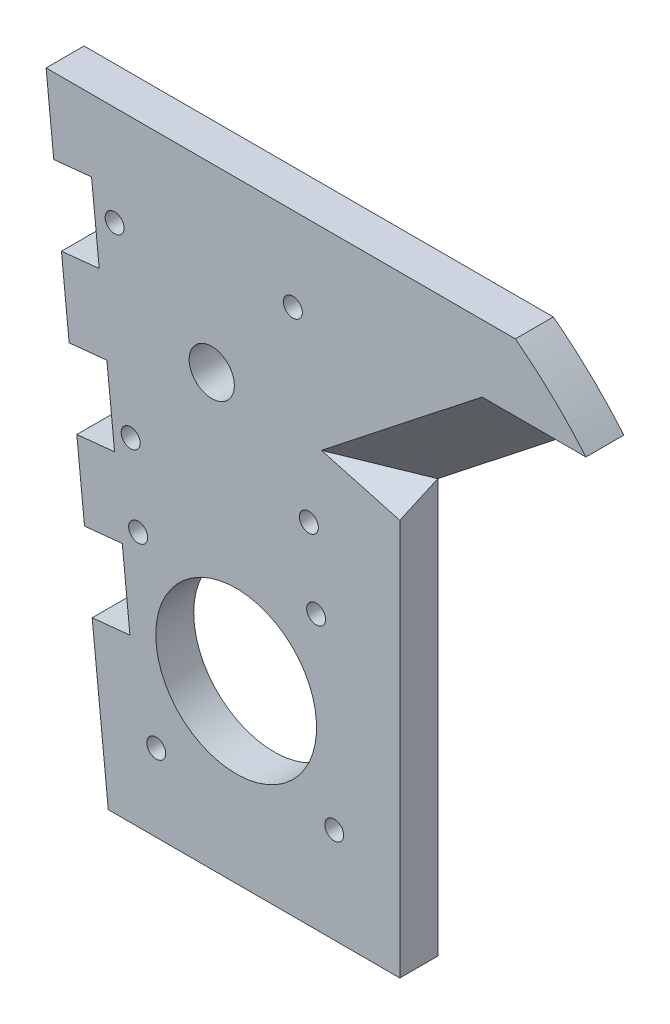
SolidWorks part; units mm, degrees
ref_plane "Front Plane" through (0, 0, 0) normal (0, 0, 1) x (1, 0, 0)
ref_plane "Top Plane" through (0, 0, 0) normal (0, 1, 0) x (1, 0, 0)
ref_plane "Right Plane" through (0, 0, 0) normal (1, 0, 0) x (0, 0, -1)
sketch "Sketch1" plane through (0, 0, 0) normal (0, 0, 1) x (1, 0, 0)
  line L0 (-43.6414, 47.6599) -> (-41.6177, 27.7626)
  line L1 (-43.6414, 47.6599) -> (80, 47.6599)
  line L2 (-37.5704, -12.0321) -> (-27.6217, -11.0203)
  line L3 (-27.2617, -113.389) -> (95, -113.389)
  line L4 (95, 30) -> (95, -113.389)
  line L5 (71.2187, 30) -> (98.5875, 30) construction
  line L6 (-18.1149, -203.3229) -> (-5.8407, -324.0059) construction
  line L7 (-41.6177, 27.7626) -> (-31.6691, 28.7744)
  line L8 (-31.6691, 28.7744) -> (-29.6454, 8.8771)
  line L9 (-29.6454, 8.8771) -> (-39.594, 7.8652)
  line L10 (-39.594, 7.8652) -> (-37.5704, -12.0321)
  line L11 (-27.6217, -11.0203) -> (-25.598, -30.9176)
  line L12 (-25.598, -30.9176) -> (-35.5467, -31.9295)
  line L13 (-35.5467, -31.9295) -> (-33.523, -51.8268)
  line L14 (-33.523, -51.8268) -> (-23.5743, -50.815)
  line L15 (-23.5743, -50.815) -> (-21.5506, -70.7123)
  line L16 (-21.5506, -70.7123) -> (-31.4993, -71.7242)
  line L17 (-31.4993, -71.7242) -> (-27.2617, -113.389)
  line L18 (71.2187, 30) -> (98.5875, 30) construction
  line L19 (95, 30) -> (98.5875, 30)
  circle A0 centre (0, 0) radius 5.9585
  spline S0 degree 2 poles (80, 47.6599) (90.2611, 39.8512) (98.5875, 30) knots 0 0 0 1 1 1
  dimension "D1" = 95
extrude "Boss-Extrude1" add sketch "Sketch1" along normal blind 10
ref_axis "Axis1" through (-681.2985, -580.132, 0) along (0.7856, 0.6188, 0)
sketch "Sketch3" plane through (0, 0, 0) normal (0, 0, -1) x (-1, 0, 0)
  line L0 (-95, 30) -> (-65, 30)
  line L1 (-95, -113.389) -> (-95, 30) construction
  line L2 (-65, 30) -> (-28, 0.8563)
  line L3 (-28, -15) -> (-95, -15)
  line L4 (-95, -15) -> (-95, 30)
  line L5 (681.2985, -580.132) -> (-401.1924, 272.512) construction
  line L6 (-28, 0.8563) -> (-28, -15)
  dimension "D1" = 30
  dimension "D2" = 30
  dimension "D3" = 45
  dimension "D4" = 67
sketch "Sketch4" plane through (0, 0, 0) normal (0, 0, -1) x (-1, 0, 0)
  line L0 (0, 0) -> (-6.4368, -67.1924) construction
  line L1 (-3.2184, -33.5962) -> (-50.6414, -29.0532) construction
  circle A0 centre (-6.4368, -67.1924) radius 21.1868
  circle A1 centre (25.5857, 21.365) radius 2.5
  circle A2 centre (-21.365, 25.5857) radius 2.5
  circle A3 centre (-6.4368, -67.1924) radius 3.175 construction
  circle A4 centre (14.6273, -93.0263) radius 2.5 construction
  circle A5 centre (-32.2708, -88.2565) radius 2.5 construction
  circle A6 centre (19.3971, -46.1283) radius 2.5 construction
  circle A7 centre (-27.501, -41.3584) radius 2.5 construction
  circle A8 centre (14.6273, -93.0263) radius 2.5
  circle A9 centre (-32.2708, -88.2565) radius 2.5
  circle A10 centre (19.3971, -46.1283) radius 2.5
  circle A11 centre (-27.501, -41.3584) radius 2.5
  circle A12 centre (-25.5857, -21.365) radius 2.5
  circle A13 centre (21.365, -25.5857) radius 2.5
extrude "Cut-Extrude4" cut sketch "Sketch4" against normal blind 10
sketch "Sketch5" plane through (-775.1664, -380.1547, 157.4414) normal (0.3654, -0.4639, 0.807) x (0.899, -0.0492, -0.4353)
  line L0 (830.5963, 510.2094) -> (803.6276, 502.9612) construction
  line L1 (845.9324, 510.7378) -> (653.1914, 500.0195)
  line L2 (845.9324, 510.7378) -> (845.9324, 468.7472)
  line L3 (845.9324, 468.7472) -> (653.1914, 468.7472)
  line L4 (653.1914, 500.0195) -> (653.1914, 468.7472)
  line L5 (830.5963, 510.2094) -> (803.6276, 502.9612) construction
  line L8 (804.8653, 508.454) -> (834.1696, 510.0836)
  line L9 (829.4687, 515.0665) -> (804.8653, 508.454)
  line L10 (804.8653, 508.454) -> (834.1696, 510.0836) construction
  spline S1 degree 2 poles (684.7348, -478.6879) (1410.3426, 1033.8467) (-168.4762, 451.0398) knots 0.486074 0.486074 0.486074 0.513978 0.513978 0.513978 only from (834.1696, 510.0836) to (829.4687, 515.0665)
  point P9 (829.0739, 509.8003)
  dimension "D1" = 0
extrude "Cut-Extrude5" cut sketch "Sketch5" along normal blind 24
sketch "Sketch6" plane through (0, 30, 0) normal (0, -1, 0) x (1, 0, 0)
  line L0 (95, 10) -> (71.2187, 10)
  line L1 (71.2187, 10) -> (98.5875, 10) construction
  line L2 (71.2187, 10) -> (93.3065, 0)
  line L3 (95, 0) -> (65, 0) construction
  line L4 (95, 0) -> (98.5875, 0)
  line L5 (98.5875, 0) -> (98.5875, 10)
  line L6 (98.5875, 10) -> (95, 10)
  line L7 (95, 10) -> (95, 0)
  line L8 (95, 0) -> (98.5875, 0)
  line L9 (98.5875, 0) -> (98.5875, 10)
  line L10 (98.5875, 10) -> (95, 10)
  line L12 (93.3065, 0) -> (95, 0)
  line L13 (93.3065, 0) -> (95, 0)
  line M5 (95, 0) -> (98.5875, 0)
  line M6 (98.5875, 0) -> (98.5875, 10)
  line M7 (98.5875, 10) -> (95, 10)
  line M8 (95, 10) -> (95, 0)
  dimension "D1" = 0
extrude "Cut-Extrude8" cut sketch "Sketch6" along normal blind 24 contours M8 M5 M6 M7 | L2 L12 L0 M8 region at (87.0354, 30, 6.4451) region at (96.7938, 30, 5)
sketch "Sketch7" plane through (0, 0, 10) normal (0, 0, 1) x (1, 0, 0)
  line L1 (95, -113.389) -> (49.5551, -113.389)
  line L2 (95, -113.389) -> (95, 0)
  line L3 (95, 0) -> (49.5551, -4.4616)
  line L4 (49.5551, -113.389) -> (49.5551, -4.4616)
extrude "Cut-Extrude9" cut sketch "Sketch7" against normal blind 24
